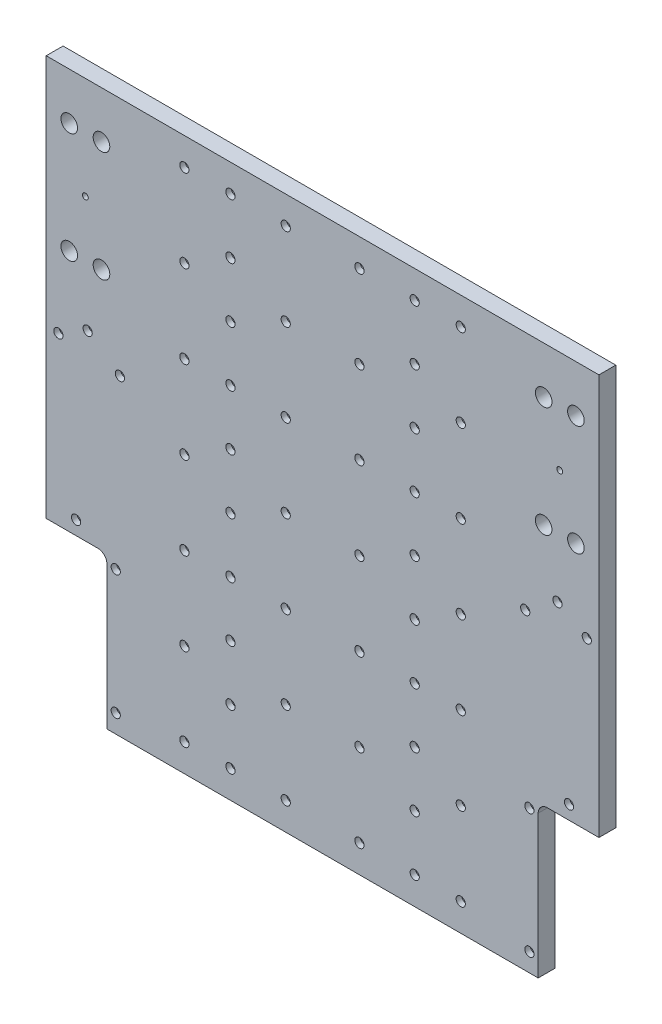
SolidWorks part; units mm, degrees
ref_plane "Front Plane" through (0, 0, 0) normal (0, 0, 1) x (1, 0, 0)
ref_plane "Top Plane" through (0, 0, 0) normal (0, 1, 0) x (1, 0, 0)
ref_plane "Right Plane" through (0, 0, 0) normal (1, 0, 0) x (0, 0, -1)
sketch "Sketch1" plane through (0, 0, 0) normal (0, 0, 1) x (1, 0, 0)
  line L1 (-300, 300) -> (300, 300)
  line L2 (-300, 300) -> (-300, -300)
  line L3 (-300, -300) -> (300, -300)
  line L4 (300, 300) -> (300, -300)
  dimension "D1" = 600
extrude "Boss-Extrude1" add sketch "Sketch1" along normal blind 18.3
sketch "Sketch2" plane through (0, 0, 0) normal (0, 0, -1) x (-1, 0, 0)
  line L0 (300, -300) -> (-300, -300) construction
  line L1 (300, 300) -> (300, -300) construction
  line L2 (234.05, -135) -> (300, -135) construction
  line L3 (234.05, -300) -> (234.05, -125) construction
  line L4 (-234.05, -125) -> (-234.05, -300) construction
  line L5 (-234.05, -135) -> (-300, -135) construction
  line L6 (300, -300) -> (234.05, -300)
  line L7 (300, -135) -> (300, -300)
  line L8 (234.05, -135) -> (300, -135)
  line L9 (234.05, -300) -> (234.05, -135)
  line L10 (-234.05, -135) -> (-234.05, -300)
  line L11 (-234.05, -135) -> (-300, -135)
  line L12 (-234.05, -300) -> (-300, -300)
  line L13 (-300, -135) -> (-300, -300)
extrude "Cut-Extrude1" cut sketch "Sketch2" against normal through all
fillet "Fillet1" radius 10 2 edges at (-234.05, -135, 9.15) (234.05, -135, 9.15)
sketch "Sketch5" plane through (0, 0, 0) normal (0, 0, -1) x (-1, 0, 0)
  circle A0 centre (240, 249) radius 9.017 construction
  circle A1 centre (275, 249) radius 9.017 construction
  circle A2 centre (257.5, 189) radius 3.175 construction
  circle A3 centre (275, 129) radius 9.017 construction
  circle A4 centre (240, 129) radius 9.017 construction
  circle A5 centre (-275, 129) radius 9.017 construction
  circle A6 centre (-240, 129) radius 9.017 construction
  circle A7 centre (-257.5, 189) radius 3.175 construction
  circle A8 centre (-275, 249) radius 9.017 construction
  circle A9 centre (-240, 249) radius 9.017 construction
  circle A10 centre (240, 249) radius 9.017
  circle A11 centre (275, 249) radius 9.017
  circle A12 centre (257.5, 189) radius 3.175
  circle A13 centre (275, 129) radius 9.017
  circle A14 centre (240, 129) radius 9.017
  circle A15 centre (-275, 129) radius 9.017
  circle A16 centre (-240, 129) radius 9.017
  circle A17 centre (-257.5, 189) radius 3.175
  circle A18 centre (-275, 249) radius 9.017
  circle A19 centre (-240, 249) radius 9.017
extrude "Cut-Extrude2" cut sketch "Sketch5" against normal through all
sketch "Sketch6" plane through (0, 0, 18.3) normal (0, 0, 1) x (1, 0, 0)
  line L0 (0, 0) -> (0, -72.3875)
  circle A0 centre (-150, -270) radius 2.5 construction
  circle A1 centre (-150, -180) radius 2.5 construction
  circle A2 centre (-150, -90) radius 2.5 construction
  circle A3 centre (-150, 0) radius 2.5 construction
  circle A4 centre (-150, 90) radius 2.5 construction
  circle A5 centre (-150, 180) radius 2.5 construction
  circle A6 centre (-150, 270) radius 2.5 construction
  circle A7 centre (150, 270) radius 2.5 construction
  circle A8 centre (150, 180) radius 2.5 construction
  circle A9 centre (150, 90) radius 2.5 construction
  circle A10 centre (150, 0) radius 2.5 construction
  circle A11 centre (150, -90) radius 2.5 construction
  circle A12 centre (150, -180) radius 2.5 construction
  circle A13 centre (150, -270) radius 2.5 construction
  circle A14 centre (-150, -270) radius 2.5
  circle A15 centre (-150, -180) radius 2.5
  circle A16 centre (-150, -90) radius 2.5
  circle A17 centre (-150, 0) radius 2.5
  circle A18 centre (-150, 90) radius 2.5
  circle A19 centre (-150, 180) radius 2.5
  circle A20 centre (-150, 270) radius 2.5
  circle A21 centre (150, 270) radius 2.5
  circle A22 centre (150, 180) radius 2.5
  circle A23 centre (150, 90) radius 2.5
  circle A24 centre (150, 0) radius 2.5
  circle A25 centre (150, -90) radius 2.5
  circle A26 centre (150, -180) radius 2.5
  circle A27 centre (150, -270) radius 2.5
  circle A28 centre (40, 270) radius 2.5
  circle A29 centre (40, 180) radius 2.5
  circle A30 centre (40, 0) radius 2.5
  circle A31 centre (40, -90) radius 2.5
  circle A32 centre (40, -180) radius 2.5
  circle A33 centre (40, 90) radius 2.5
  circle A34 centre (40, -270) radius 2.5
  circle A35 centre (-40, -270) radius 2.5
  circle A36 centre (-40, 90) radius 2.5
  circle A37 centre (-40, -180) radius 2.5
  circle A38 centre (-40, -90) radius 2.5
  circle A39 centre (-40, 0) radius 2.5
  circle A40 centre (-40, 180) radius 2.5
  circle A41 centre (-40, 270) radius 2.5
sketch "Sketch7" plane through (0, 0, 18.3) normal (0, 0, 1) x (1, 0, 0)
  line L16 (0, -65.4775) -> (0, 65.4775) construction
  line L17 (215, -48.8) -> (215, -44.1371) construction
  line L18 (238.4315, 12.4315) -> (300, 74) construction
  line L19 (300, 74) -> (300, 45.7157) construction
  line L20 (300, 45.7157) -> (252.5736, -1.7107) construction
  line L21 (235, -44.1371) -> (300, -44.1371) construction
  line L22 (300, -44.1371) -> (300, -48.8) construction
  line L24 (300, -48.8) -> (300, -64.1371) construction
  line L25 (300, -64.1371) -> (235, -64.1371) construction
  line L26 (235, -64.1371) -> (235, -105) construction
  line L27 (235, -105) -> (300, -105) construction
  line L28 (300, -105) -> (300, -135) construction
  line L29 (300, -135) -> (234.05, -135) construction
  line L30 (234.05, -135) -> (234.05, -125) construction
  line L31 (234.05, -125) -> (215, -125) construction
  line L32 (215, -125) -> (215, -48.8) construction
  line L34 (-300, -64.1371) -> (-300, -48.8) construction
  line L36 (-215, -48.8) -> (-215, -125) construction
  line L37 (-215, -125) -> (-234.05, -125) construction
  line L38 (-234.05, -125) -> (-234.05, -135) construction
  line L39 (-234.05, -135) -> (-300, -135) construction
  line L40 (-300, -135) -> (-300, -105) construction
  line L41 (-300, -105) -> (-235, -105) construction
  line L42 (-235, -105) -> (-235, -64.1371) construction
  line L43 (-235, -64.1371) -> (-300, -64.1371) construction
  line L44 (-215, -44.1371) -> (-215, -48.8) construction
  line L46 (-300, -48.8) -> (-300, -44.1371) construction
  line L47 (-300, -44.1371) -> (-235, -44.1371) construction
  line L48 (-252.5736, -1.7107) -> (-300, 45.7157) construction
  line L49 (-300, 45.7157) -> (-300, 74) construction
  line L50 (-300, 74) -> (-238.4315, 12.4315) construction
  line L51 (215, -48.8) -> (215, -44.1371)
  line L52 (238.4315, 12.4315) -> (300, 74)
  line L53 (300, 74) -> (300, 45.7157)
  line L54 (300, 45.7157) -> (252.5736, -1.7107)
  line L55 (235, -44.1371) -> (300, -44.1371)
  line L56 (300, -44.1371) -> (300, -48.8)
  line L58 (300, -48.8) -> (300, -64.1371)
  line L59 (300, -64.1371) -> (235, -64.1371)
  line L60 (235, -64.1371) -> (235, -105)
  line L61 (235, -105) -> (300, -105)
  line L62 (300, -105) -> (300, -135)
  line L63 (300, -135) -> (234.05, -135)
  line L64 (234.05, -135) -> (234.05, -125)
  line L65 (234.05, -125) -> (215, -125)
  line L66 (215, -125) -> (215, -48.8)
  line L68 (-300, -64.1371) -> (-300, -48.8)
  line L70 (-215, -48.8) -> (-215, -125)
  line L71 (-215, -125) -> (-234.05, -125)
  line L72 (-234.05, -125) -> (-234.05, -135)
  line L73 (-234.05, -135) -> (-300, -135)
  line L74 (-300, -135) -> (-300, -105)
  line L75 (-300, -105) -> (-235, -105)
  line L76 (-235, -105) -> (-235, -64.1371)
  line L77 (-235, -64.1371) -> (-300, -64.1371)
  line L78 (-215, -44.1371) -> (-215, -48.8)
  line L80 (-300, -48.8) -> (-300, -44.1371)
  line L81 (-300, -44.1371) -> (-235, -44.1371)
  line L82 (-252.5736, -1.7107) -> (-300, 45.7157)
  line L83 (-300, 45.7157) -> (-300, 74)
  line L84 (-300, 74) -> (-238.4315, 12.4315)
  circle A0 centre (224.525, -145) radius 2.5
  circle A1 centre (224.525, -280) radius 2.5
  circle A2 centre (-224.525, -145) radius 2.5
  circle A3 centre (-224.525, -280) radius 2.5
  arc A4 (238.4315, 12.4315) -> (215, -44.1371) centre (295, -44.1371) ccw construction
  arc A5 (252.5736, -1.7107) -> (235, -44.1371) centre (295, -44.1371) ccw construction
  arc A6 (-235, -44.1371) -> (-252.5736, -1.7107) centre (-295, -44.1371) ccw construction
  arc A7 (-215, -44.1371) -> (-238.4315, 12.4315) centre (-295, -44.1371) ccw construction
  arc A8 (238.4315, 12.4315) -> (215, -44.1371) centre (295, -44.1371) ccw
  arc A9 (252.5736, -1.7107) -> (235, -44.1371) centre (295, -44.1371) ccw
  arc A10 (-235, -44.1371) -> (-252.5736, -1.7107) centre (-295, -44.1371) ccw
  arc A11 (-215, -44.1371) -> (-238.4315, 12.4315) centre (-295, -44.1371) ccw
  circle A14 centre (286.8234, 45.7157) radius 2.5
  circle A15 centre (267.5, -120) radius 2.5
  circle A16 centre (-267.5, -120) radius 2.5
  circle A17 centre (-286.8234, 45.7157) radius 2.5
hole_wizard "CBORE for M5 SHCS1" positions "Sketch3" profile "Sketch4" counterbore size "M5" standard "ANSI Metric"
sketch "Sketch3" plane through (0, 0, 18.3) normal (0, 0, 1) x (1, 0, 0)
  point P0 (-100, 210)
  point P3 (-100, 270)
  point P6 (100, 270)
  point P9 (100, 210)
  point P12 (100, 150)
  point P15 (-100, 150)
  point P18 (-100, 90)
  point P21 (100, 90)
  point P24 (100, 30)
  point P27 (-100, 30)
  point P30 (-255, 64)
  point P33 (-220, 39)
  point P36 (255, 64)
  point P39 (220, 39)
  point P42 (100, -30)
  point P45 (-100, -30)
  point P48 (-100, -90)
  point P51 (100, -90)
  point P54 (100, -150)
  point P57 (-100, -150)
  point P60 (-100, -210)
  point P63 (100, -210)
  point P66 (100, -270)
  point P69 (-100, -270)
  point P72 (150, -270)
  point P75 (150, -180)
  point P78 (150, -90)
  point P81 (150, 0)
  point P84 (150, 90)
  point P87 (150, 180)
  point P90 (150, 270)
  point P93 (40, 270)
  point P96 (40, 180)
  point P99 (-40, 180)
  point P102 (-40, 270)
  point P105 (-150, 270)
  point P108 (-150, 180)
  point P111 (-150, 90)
  point P114 (-40, 90)
  point P117 (40, 90)
  point P120 (40, 0)
  point P123 (-40, 0)
  point P126 (-40, -90)
  point P129 (40, -90)
  point P132 (-150, -90)
  point P135 (-150, 0)
  point P138 (-150, -90)
  point P141 (-150, 0)
  point P143 (-220, 39)
  point P145 (-255, 64)
  point P147 (-150, -90)
  point P149 (-150, -180)
  point P152 (-150, -270)
  point P155 (-40, -270)
  point P158 (-40, -180)
  point P161 (40, -180)
  point P164 (40, -270)
  point P167 (224.525, -280)
  point P170 (224.525, -145)
  point P173 (-224.525, -145)
  point P176 (-224.525, -280)
  point P179 (-267.5, -120)
  point P182 (-286.8234, 45.7157)
  point P185 (286.8234, 45.7157)
  point P188 (267.5, -120)
sketch "Sketch4" plane through (-100, 210, 18.3) normal (1, 0, 0) x (0, -1, 0)
  line L0 (0, 0) -> (0, 30)
  line L1 (0, 30) -> (2.75, 28.3476)
  line L2 (2.75, 28.3476) -> (2.75, 6)
  line L3 (2.75, 6) -> (5, 6)
  line L4 (5, 6) -> (5, 0)
  line L5 (5, 0) -> (0, 0)
  line L10 (0, 30) -> (-2.75, 28.3476) construction
  line L11 (0, -6.35) -> (0, 107.95) construction
  dimension "Hole Dia." = 5.5
  dimension "Hole Depth" = 30
  dimension "C'Bore Dia." = 10
  dimension "C'Bore Depth" = 6
  dimension "Drill Angle" = 118
sketch "Sketch8" plane through (0, 0, 18.3) normal (0, 0, 1) x (1, 0, 0)
  circle A0 centre (-40, 0) radius 3.175
  circle A1 centre (40, 0) radius 3.175
extrude "Cut-Extrude3" cut sketch "Sketch8" against normal through all
sketch "Sketch10" plane through (0, 0, 18.3) normal (0, 0, 1) x (1, 0, 0)
  line L1 (-234.05, -300) -> (234.05, -300) construction
  line L3 (-300, 300) -> (-300, -135) construction
  line L5 (300, -135) -> (300, 300) construction
  line L6 (-300, -135) -> (-244.05, -135) construction
  line L7 (244.05, -135) -> (300, -135) construction
  line L8 (234.05, -300) -> (234.05, -145) construction
  line L9 (-234.05, -145) -> (-234.05, -300) construction
  line L10 (-300, 20) -> (-300, -135)
  line L11 (-300, -135) -> (-244.05, -135)
  line L12 (300, -135) -> (300, 20)
  line L13 (244.05, -135) -> (300, -135)
  line L14 (234.05, -300) -> (234.05, -145)
  line L15 (-234.05, -145) -> (-234.05, -300)
  line L16 (-234.05, -300) -> (234.05, -300)
  arc A0 (244.05, -135) -> (234.05, -145) centre (244.05, -145) ccw construction
  arc A1 (-234.05, -145) -> (-244.05, -135) centre (-244.05, -145) ccw construction
  arc A2 (244.05, -135) -> (234.05, -145) centre (244.05, -145) ccw
  arc A3 (-234.05, -145) -> (-244.05, -135) centre (-244.05, -145) ccw
sketch "Sketch11" plane through (0, 0, 18.3) normal (0, 0, 1) x (1, 0, 0)
  line L0 (-300, 300) -> (-300, -135) construction
  line L1 (300, -135) -> (300, 300) construction
  line L2 (300, 300) -> (-300, 300) construction
  line L3 (-300, 300) -> (-300, -10)
  line L4 (300, -10) -> (300, 300)
  line L5 (300, 300) -> (-300, 300)
